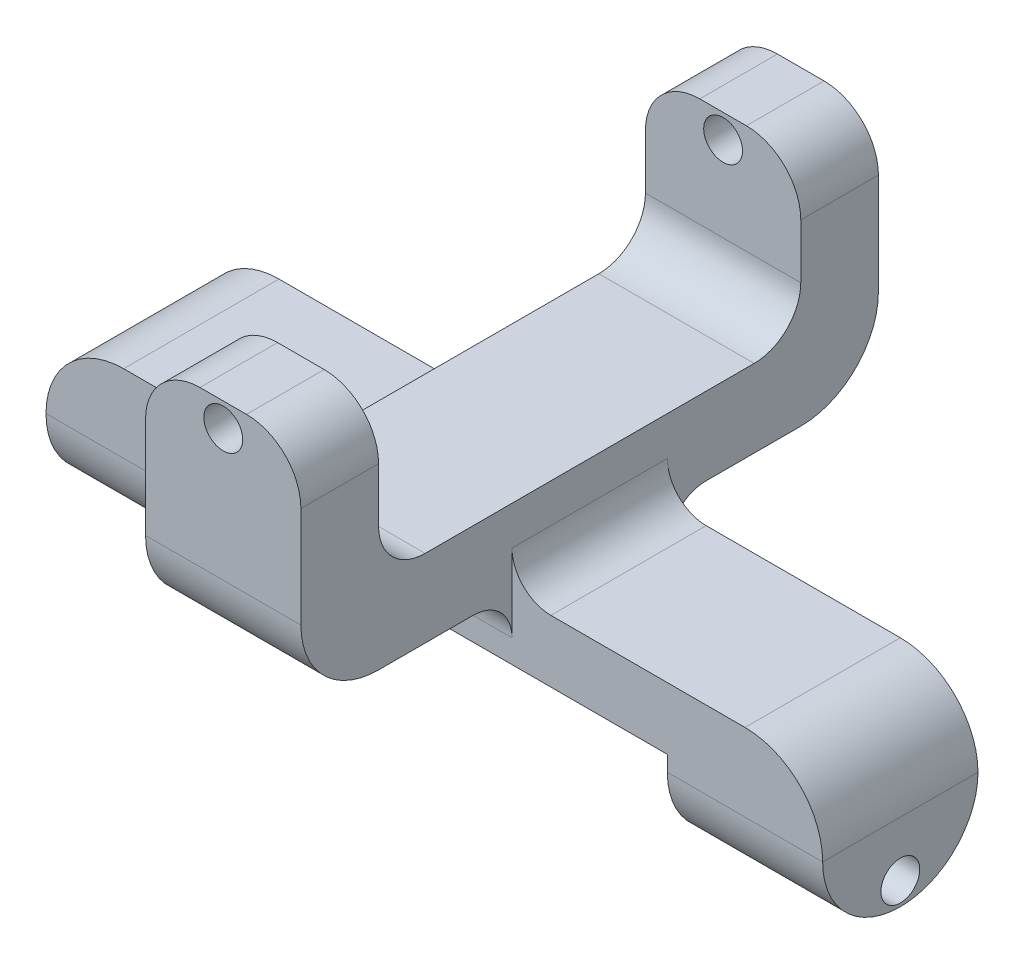
SolidWorks part; units mm, degrees
ref_plane "Front Plane" through (0, 0, 0) normal (0, 0, 1) x (1, 0, 0)
ref_plane "Top Plane" through (0, 0, 0) normal (0, 1, 0) x (1, 0, 0)
ref_plane "Right Plane" through (0, 0, 0) normal (1, 0, 0) x (0, 0, -1)
sketch "Sketch1" plane through (0, 0, 0) normal (0, 1, 0) x (1, 0, 0)
  line L0 (0, -5) -> (0, 5) construction
  line L1 (-25, -5) -> (25, -5)
  line L2 (-25, -5) -> (-25, 5)
  line L3 (-25, 5) -> (25, 5)
  line L4 (25, -5) -> (25, 5)
  line L5 (-25, 0) -> (25, 0) construction
  line L6 (-15, 5) -> (-15, -5) construction
  line L7 (15, 5) -> (15, -5) construction
  point P8 (0, 0)
  dimension "D1" = 10
  dimension "D2" = 50
  dimension "D3" = 10
  dimension "D4" = 10
extrude "Boss-Extrude1" add sketch "Sketch1" along normal blind 10
sketch "Sketch2" plane through (0, 0, 0) normal (0, -1, 0) x (1, 0, 0)
  line L0 (25, -5) -> (-25, -5) construction
  line L1 (-15, -5) -> (15, -5)
  line L2 (-15, -5) -> (-15, 5)
  line L3 (-15, 5) -> (15, 5)
  line L4 (15, -5) -> (15, 5)
  line L5 (-25, 5) -> (25, 5) construction
  line L6 (-25, -5) -> (-25, 5) construction
  line L7 (25, 5) -> (25, -5) construction
  dimension "D1" = 10
  dimension "D2" = 10
extrude "Cut-Extrude1" cut sketch "Sketch2" against normal blind 6
fillet "Fillet3" radius 5 4 edges at (-20, 0, -5) (20, 0, -5) (20, 0, 5) (-20, 0, 5)
sketch "Sketch3" plane through (-15, 0, 0) normal (1, 0, 0) x (0, 0, -1)
  line L0 (0, 0) -> (0, 6) construction
  line L1 (-5, 6) -> (5, 6) construction
  line L2 (-3.5355, 1.4645) -> (3.5355, 1.4645) construction
  arc A0 (-5, 5) -> (0, 0) centre (0, 5) ccw construction
  arc A1 (0, 0) -> (5, 5) centre (0, 5) ccw construction
  circle A2 centre (0, 1.4645) radius 1.25
  dimension "D1" = 2.5
  dimension "D2" = 7.0711
extrude "Cut-Extrude2" cut sketch "Sketch3" against normal through all both and the other way through all
fillet "Fillet4" radius 5 2 edges at (25, 10, 0) (-25, 10, 0)
sketch "Sketch4" plane through (0, 10, 0) normal (0, 1, 0) x (1, 0, 0)
  line L0 (0, -18.59) -> (0, 18.59) construction
  line L1 (-5, 18.59) -> (5, 18.59)
  line L2 (-5, 18.59) -> (-5, -18.59)
  line L3 (-5, -18.59) -> (5, -18.59)
  line L4 (5, 18.59) -> (5, -18.59)
  line L5 (-5, 0) -> (5, 0) construction
  point P8 (0, 0)
  dimension "D1" = 0
  dimension "D2" = 10
  dimension "D3" = 37.18
extrude "Boss-Extrude2" add sketch "Sketch4" along normal blind 15
fillet "Fillet7" radius 2.5 2 edges at (0, 10, -5) (0, 10, 5)
sketch "Sketch5" plane through (0, 25, 0) normal (0, 1, 0) x (1, 0, 0)
  line L0 (5, -18.59) -> (5, 18.59) construction
  line L1 (5, 13.59) -> (-5, 13.59)
  line L2 (5, 13.59) -> (5, -13.59)
  line L3 (5, -13.59) -> (-5, -13.59)
  line L4 (-5, 13.59) -> (-5, -13.59)
  line L5 (-5, 18.59) -> (-5, -18.59) construction
  line L6 (5, 18.59) -> (-5, 18.59) construction
  line L7 (-5, -18.59) -> (5, -18.59) construction
  dimension "D1" = 5
  dimension "D2" = 5
extrude "Cut-Extrude3" cut sketch "Sketch5" against normal blind 10
fillet "Fillet8" radius 2.5 2 edges at (5, 10, 0) (-5, 10, 0)
sketch "Sketch6" plane through (0, 0, 13.59) normal (0, 0, -1) x (-1, 0, 0)
  line L0 (0, 25) -> (0, 15) construction
  line L3 (-5, 23.4649) -> (5, 23.4649) construction
  line L6 (-5, 15) -> (-5, 25) construction
  line L7 (5, 15) -> (5, 25) construction
  line L8 (5, 25) -> (-5, 25) construction
  line L9 (5, 15) -> (-5, 15) construction
  circle A0 centre (0, 23.4649) radius 1.25
  point P14 (0, 23.4649)
  dimension "D1" = 2.5
extrude "Cut-Extrude4" cut sketch "Sketch6" against normal through all both and the other way through all
fillet "Fillet9" radius 3.5 4 edges at (-5, 25, -16.09) (5, 25, -16.09) (5, 25, 16.09) (-5, 25, 16.09)
fillet "Fillet10" radius 5 2 edges at (0, 10, 18.59) (0, 10, -18.59)
fillet "Fillet11" radius 3 2 edges at (0, 15, 13.59) (0, 15, -13.59)
